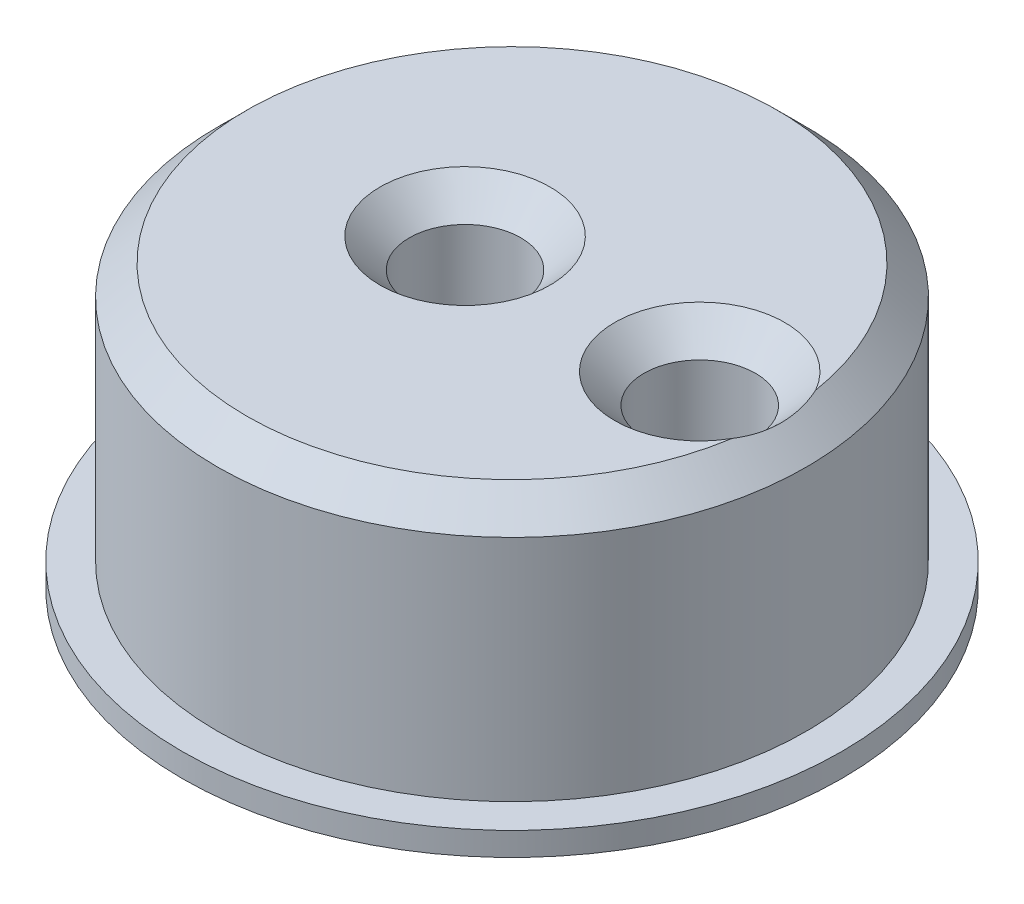
SolidWorks part; units mm, degrees
ref_plane "前视基准面" through (0, 0, 0) normal (0, 0, 1) x (1, 0, 0)
ref_plane "上视基准面" through (0, 0, 0) normal (0, 1, 0) x (1, 0, 0)
ref_plane "右视基准面" through (0, 0, 0) normal (1, 0, 0) x (0, 0, -1)
other "Configuration Table"
sketch "草图1" plane through (0, 0, 0) normal (0, 1, 0) x (1, 0, 0)
  line L0 (1.2, 6.4178) -> (1.2, -6.4114) construction
  line L1 (-5.7349, 0) -> (5.8104, 0) construction
  circle A0 centre (0, 0) radius 5.02
  circle A1 centre (3.2, 0) radius 0.95
  circle A2 centre (-0.8, 0) radius 0.95
  dimension "D1" = 10.04
  dimension "D3" = 4
  dimension "D4" = 1.9
  dimension "D2" = 1.2
extrude "凸台-拉伸1" add sketch "草图1" along normal blind 4.4
sketch "草图3" plane through (0, 0, 0) normal (0, -1, 0) x (1, 0, 0)
  circle A0 centre (3.2, 0) radius 0.95 construction
  circle A1 centre (0, 0) radius 5.02 construction
  circle A3 centre (-0.8, 0) radius 0.95 construction
  circle A4 centre (3.2, 0) radius 0.95
  circle A5 centre (-0.8, 0) radius 0.95
  circle A6 centre (0, 0) radius 5.02 construction
  circle A7 centre (0, 0) radius 5.62
  dimension "D1" = 0.6
extrude "凸台-拉伸2" add sketch "草图3" along normal blind 0.4
chamfer "倒角1" distance 0.5 angle 45 5 edges at (0, 4.4, 5.02) (-0.8, 4.4, -0.95) (3.2, 4.4, 0.95) (-0.8, -0.4, -0.95) (3.2, -0.4, -0.95)
ref_axis "基准轴1" through (0, 3.9, 0) along (0, -1, 0)
sketch "草图2" plane through (0, 0, 0) normal (0, 1, 0) x (1, 0, 0)
  line L0 (-5.9042, 0) -> (6.2358, 0) construction
